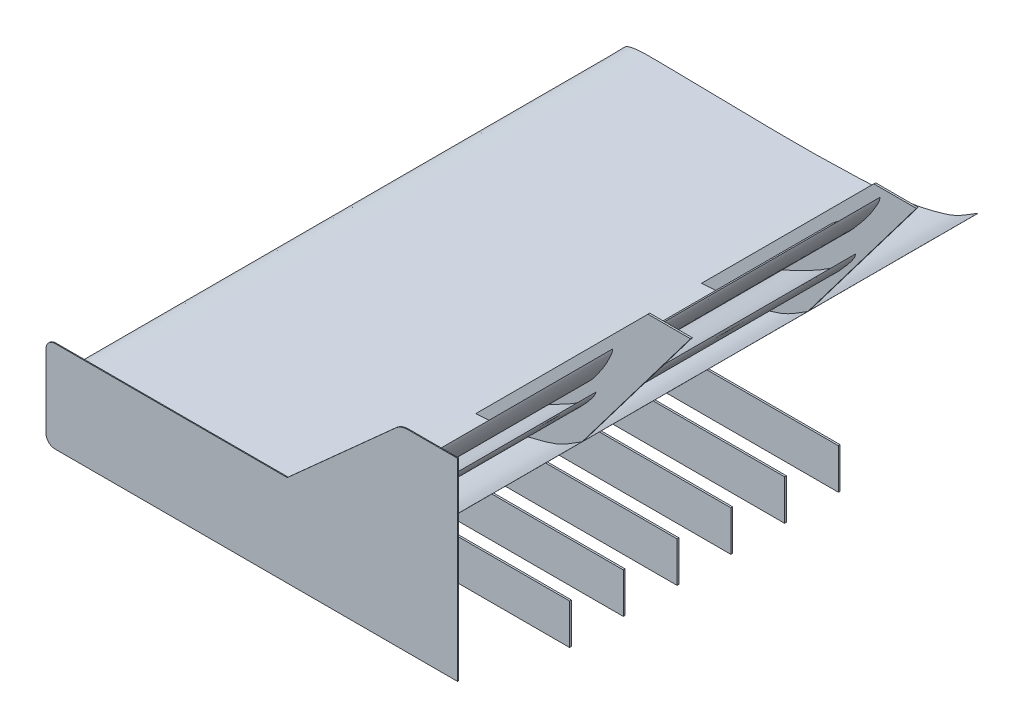
SolidWorks part; units mm, degrees
ref_plane "Front Plane" through (0, 0, 0) normal (0, 0, 1) x (1, 0, 0)
ref_plane "Top Plane" through (0, 0, 0) normal (0, 1, 0) x (1, 0, 0)
ref_plane "Right Plane" through (0, 0, 0) normal (1, 0, 0) x (0, 0, -1)
sketch "Sketch1" plane through (0, 0, 0) normal (0, 0, 1) x (1, 0, 0)
  line L0 (0, 0) -> (100, 0) construction
  line L1 (1.25, 16.6531) -> (1.25, -38.4553) construction
  line L2 (2.5, 17.9055) -> (2.5, -38.4614) construction
  line L3 (0, 16.6233) -> (0, -25.6938) construction
  line L4 (2.5, -38.4553) -> (2.5, 17.9055) construction
  line L6 (5, 17.9055) -> (5, -38.4553) construction
  line L8 (7.5, -38.4553) -> (7.5, 17.9055) construction
  line L10 (10, 17.9055) -> (10, -38.4553) construction
  line L12 (15, -38.4553) -> (15, 17.9055) construction
  line L14 (20, 17.9055) -> (20, -38.4553) construction
  line L16 (30, -38.4553) -> (30, 17.9055) construction
  line L18 (40, 17.9055) -> (40, -38.4553) construction
  line L20 (50, -38.4553) -> (50, 17.9055) construction
  line L22 (60, 17.9055) -> (60, -38.4553) construction
  line L24 (70, -38.4553) -> (70, 17.9055) construction
  line L26 (80, 17.9055) -> (80, -38.4553) construction
  line L28 (90, -38.4553) -> (90, 17.9055) construction
  line L30 (95, 17.9055) -> (95, -38.4553) construction
  line L32 (100, -38.4553) -> (100, 17.9055) construction
  spline S2 degree 3 poles (94.3673, -3.5638) (102.8561, 1.5222) (94.504, -2.988) (88.8138, -4.3065) (79.9056, -5.4947) (70.0198, -5.0741) (59.9849, -4.387) (49.9902, -3.5342) (39.9927, -2.4103) (30.0039, -1.1606) (21.6652, -0.2167) (14.9997, 0.5924) (10.0103, 1.184) (5.8366, 1.6528) (2.898, 1.5692) (0.8648, 1.1108) (-0.6238, -1.2668) (0.9385, -3.7627) (2.7533, -5.9838) (4.8768, -7.8493) (7.4255, -9.5789) (10.7358, -11.3943) (14.9019, -13.1207) (21.5668, -15.0457) (29.9416, -16.4142) (39.9918, -17.0298) (50.051, -16.6825) (60.0771, -15.2123) (70.1301, -12.7919) (80.007, -9.774) (88.8716, -6.1499) (94.3673, -3.5638) (102.8561, 1.5222) (94.504, -2.988) knots -0.105257 -0.054131 -0.027635 0 0.026268 0.051016 0.098804 0.146246 0.193788 0.241403 0.289125 0.336907 0.384666 0.408554 0.432437 0.456234 0.468112 0.474323 0.485191 0.50162 0.510955 0.52691 0.541278 0.554823 0.580548 0.60527 0.653411 0.700937 0.748406 0.796324 0.845052 0.894743 0.945869 0.972365 1 1.026268 1.051016 1.098804 only from (100, -0.1) to (100, -0.1)
  point P37 (0, -0.86)
  point P38 (1.25, -4.09)
  point P40 (1.25, 1.06)
  point P41 (2.5, 1.45)
  point P42 (5, -7.86)
  point P43 (2.5, -5.61)
  point P44 (5, 1.59)
  point P45 (7.5, -9.57)
  point P46 (7.5, 1.44)
  point P47 (10, 1.18)
  point P48 (15, 0.59)
  point P49 (15, -13.05)
  point P50 (20, -0.01)
  point P51 (20, -14.52)
  point P52 (30, -1.18)
  point P53 (30, -16.25)
  point P54 (40, -2.39)
  point P55 (10, -10.95)
  point P56 (40, -16.87)
  point P57 (40, -2.39)
  point P58 (50, -3.49)
  point P59 (50, -16.5)
  point P60 (60, -4.36)
  point P61 (60, -15.07)
  point P62 (70, -5.03)
  point P63 (70, -12.72)
  point P64 (80, -5.19)
  point P65 (80, -9.6)
  point P66 (90, -3.97)
  point P67 (90, -5.58)
  point P68 (95, -2.48)
  point P69 (95, -3.09)
  point P70 (100, -0.1)
  point P71 (100, -0.2)
  dimension "D1" = 100
  dimension "D2" = 1.25
  dimension "D3" = 2.5
  dimension "D4" = 2.5
  dimension "D5" = 7.5
  dimension "D6" = 10
  dimension "D7" = 15
  dimension "D8" = 5
  dimension "D9" = 10
  dimension "D10" = 10
  dimension "D11" = 10
  dimension "D12" = 10
  dimension "D13" = 10
  dimension "D14" = 10
  dimension "D15" = 10
  dimension "D16" = 5
  dimension "D17" = 5
curve "Curve1"
  spline degree 3 poles (98.5502, -0.8292, 0) (100.5299, 0.3794, 0) (99.1462, -0.6768, 0) (98.4443, -1.2755, 0) (97.3097, -2.0642, 0) (96.0009, -2.7117, 0) (94.4298, -3.3947, 0) (92.569, -4.0837, 0) (90.4012, -4.8122, 0) (87.9505, -5.5478, 0) (85.2749, -6.304, 0) (82.4359, -7.0338, 0) (79.5022, -7.7406, 0) (76.5208, -8.4057, 0) (73.5219, -9.0393, 0) (70.5175, -9.6161, 0) (67.5077, -10.1489, 0) (64.4881, -10.6321, 0) (61.4395, -11.0484, 0) (58.3521, -11.4274, 0) (55.2125, -11.781, 0) (52.0112, -12.0861, 0) (48.7533, -12.37, 0) (45.4544, -12.6663, 0) (42.1402, -12.9291, 0) (38.8572, -13.1898, 0) (35.6511, -13.4329, 0) (32.5711, -13.6325, 0) (29.6613, -13.7858, 0) (26.9506, -13.8772, 0) (24.4353, -13.8571, 0) (22.088, -13.7476, 0) (19.8826, -13.5013, 0) (17.7867, -13.168, 0) (15.7934, -12.7056, 0) (13.8906, -12.1349, 0) (12.076, -11.4655, 0) (10.3558, -10.6964, 0) (8.7488, -9.8421, 0) (7.2684, -8.933, 0) (5.9416, -8.0004, 0) (4.7755, -7.0863, 0) (3.7847, -6.217, 0) (2.957, -5.4094, 0) (2.269, -4.6735, 0) (1.728, -3.9816, 0) (1.2751, -3.3596, 0) (0.9309, -2.7719, 0) (0.6318, -2.2442, 0) (0.4105, -1.7465, 0) (0.2408, -1.2843, 0) (0.1068, -0.8552, 0) (0.0223, -0.45, 0) (-0.004, -0.0672, 0) (-0.0039, 0.3013, 0) (0.0809, 0.6622, 0) (0.2952, 0.9824, 0) (0.6315, 1.1995, 0) (1.032, 1.3336, 0) (1.4872, 1.4186, 0) (2.0055, 1.4764, 0) (2.6028, 1.5163, 0) (3.3032, 1.5313, 0) (4.1367, 1.5461, 0) (5.1573, 1.5223, 0) (6.4269, 1.4548, 0) (8.0274, 1.3654, 0) (10.0021, 1.2291, 0) (12.3384, 1.004, 0) (14.971, 0.7256, 0) (17.8195, 0.3367, 0) (20.844, -0.1077, 0) (24.0032, -0.6376, 0) (27.2668, -1.1722, 0) (30.5738, -1.7172, 0) (33.8785, -2.2723, 0) (37.1527, -2.7975, 0) (40.3807, -3.3138, 0) (43.5644, -3.7828, 0) (46.6972, -4.2145, 0) (49.7874, -4.5959, 0) (52.8339, -4.9281, 0) (55.8477, -5.1987, 0) (58.8316, -5.4085, 0) (61.7919, -5.5626, 0) (64.7329, -5.6385, 0) (67.6568, -5.6622, 0) (70.5644, -5.6128, 0) (73.4581, -5.4881, 0) (76.3366, -5.3163, 0) (79.1931, -5.05, 0) (82.0171, -4.7312, 0) (84.7804, -4.3625, 0) (87.434, -3.9036, 0) (89.9332, -3.4404, 0) (92.2075, -2.9247, 0) (94.233, -2.3848, 0) (95.9446, -1.8589, 0) (97.5056, -1.2357, 0) (98.5502, -0.8292, 0) (100.5299, 0.3794, 0) (99.1462, -0.6768, 0) knots -0.020778 -0.013318 -0.006872 0 0.003934 0.00967 0.015849 0.022782 0.030794 0.040273 0.051195 0.063508 0.076888 0.09098 0.105453 0.12007 0.134692 0.149314 0.163846 0.178433 0.193072 0.207875 0.222946 0.238282 0.253894 0.269743 0.28568 0.30147 0.316872 0.331691 0.345638 0.35857 0.370496 0.381625 0.392182 0.402235 0.411978 0.42144 0.430647 0.439636 0.448385 0.456672 0.46448 0.47158 0.477867 0.483331 0.488125 0.492267 0.495894 0.499125 0.502007 0.504569 0.506909 0.509051 0.510997 0.512815 0.514533 0.516257 0.518043 0.519896 0.521872 0.524061 0.526511 0.529332 0.532624 0.536536 0.54126 0.547229 0.554731 0.564199 0.575553 0.588316 0.602079 0.616691 0.632061 0.647918 0.664017 0.680023 0.695872 0.71147 0.726804 0.741922 0.756725 0.771359 0.785775 0.800025 0.814163 0.828192 0.842121 0.856004 0.869802 0.883566 0.897265 0.910851 0.924235 0.937151 0.949387 0.960589 0.970563 0.979222 0.986682 0.993128 1 1.003934 1.00967 1.015849 periodic
sketch "Sketch2" plane through (0, 0, 0) normal (0, 0, 1) x (1, 0, 0)
  line L0 (331.6325, -0.1558) -> (-65.7962, -45.4371) construction
  line L1 (-65.7962, -45.4371) -> (-68.337, -23.1365) construction
  line L2 (0, 0) -> (60.5483, 0) construction
  line L3 (385.2571, 82.501) -> (286.9589, 13.6718) construction
  line L4 (286.9589, 13.6718) -> (272.478, 34.3526) construction
  line L5 (331.6325, -0.1558) -> (331.6325, 76.9311) construction
  line L6 (331.6325, -0.1558) -> (397.2706, -0.1558) construction
  line L7 (412.1546, 150.4845) -> (355.5861, 93.9159) construction
  line L8 (299.294, 9.8442) -> (308.8152, 9.8442) construction
  line L9 (286.6325, 14.5606) -> (286.6325, 26.1748) construction
  line L10 (355.5861, 93.9159) -> (325.5679, 123.9341) construction
  line L11 (385.2571, 82.501) -> (439.2948, 82.501) construction
  line L12 (385.2571, 82.501) -> (385.2571, 253.7541) construction
  line L14 (360.5365, 92.501) -> (347.2815, 92.501) construction
  line L15 (355.2571, 94.5953) -> (355.2571, 86.9128) construction
  spline S1 degree 3 poles (384.8846, 81.2478) (385.5164, 83.2388) (384.4039, 80.6874) (383.6577, 79.5684) (382.5534, 77.8807) (381.234, 76.1849) (379.6159, 74.2589) (377.7366, 72.1854) (375.6004, 70.0085) (373.3094, 67.7296) (370.8484, 65.4636) (368.2936, 63.2048) (365.6704, 60.9752) (362.9606, 58.8233) (360.2036, 56.7073) (357.3809, 54.6556) (354.4918, 52.6644) (351.55, 50.7129) (348.5353, 48.8248) (345.4591, 46.9752) (342.3116, 45.1647) (339.0895, 43.3924) (335.7907, 41.6382) (332.4153, 39.904) (328.9642, 38.1714) (325.437, 36.4548) (321.8583, 34.7152) (318.229, 32.9837) (314.6045, 31.2409) (311.0296, 29.5177) (307.5607, 27.8619) (304.283, 26.2148) (301.2163, 24.6344) (298.438, 23.0944) (295.9876, 21.7059) (293.9535, 20.4794) (292.3194, 19.4647) (291.0255, 18.6563) (290.0064, 17.9765) (289.1977, 17.3878) (288.5198, 16.8905) (287.9605, 16.4397) (287.4911, 16.026) (287.1025, 15.6288) (286.8013, 15.2211) (286.6204, 14.7762) (286.6306, 14.3139) (286.7959, 13.9009) (287.0496, 13.5387) (287.3391, 13.1808) (287.7014, 12.8408) (288.1286, 12.5116) (288.6138, 12.1745) (289.1741, 11.8379) (289.8315, 11.5255) (290.5746, 11.1852) (291.4481, 10.8861) (292.4563, 10.579) (293.6392, 10.33) (295.0088, 10.1068) (296.5811, 9.9353) (298.3566, 9.8405) (300.3027, 9.8384) (302.3835, 9.9651) (304.5509, 10.2329) (306.7709, 10.6623) (309.0149, 11.2548) (311.2776, 12.005) (313.5546, 12.9239) (315.8434, 14.0403) (318.1798, 15.3178) (320.5616, 16.8273) (323.0467, 18.5404) (325.647, 20.4977) (328.4002, 22.653) (331.2889, 24.971) (334.2713, 27.4186) (337.3173, 29.9365) (340.3924, 32.4781) (343.4295, 35.0419) (346.4347, 37.5652) (349.3698, 40.0706) (352.2108, 42.5809) (354.9831, 45.0803) (357.6916, 47.5896) (360.3254, 50.1446) (362.9155, 52.7417) (365.4699, 55.3783) (367.9798, 58.0668) (370.4509, 60.7742) (372.8463, 63.4898) (375.1328, 66.1627) (377.2406, 68.7489) (379.1415, 71.1601) (380.7696, 73.3693) (382.1232, 75.3282) (383.1961, 77.0817) (384.0359, 78.6195) (384.6074, 80.1761) (384.8846, 81.2478) (385.5164, 83.2388) (384.4039, 80.6874) knots -0.015849 -0.00967 -0.003934 0 0.006872 0.013318 0.020778 0.029437 0.039411 0.050613 0.062849 0.075765 0.089149 0.102735 0.116434 0.130198 0.143996 0.157879 0.171808 0.185837 0.199975 0.214225 0.228641 0.243275 0.258078 0.273196 0.28853 0.304128 0.319977 0.335983 0.352082 0.367939 0.383309 0.397921 0.411684 0.424447 0.435801 0.445269 0.452771 0.45874 0.463464 0.467376 0.470668 0.473489 0.475939 0.478128 0.480104 0.481957 0.483743 0.485467 0.487185 0.489003 0.490949 0.493091 0.495431 0.497993 0.500875 0.504106 0.507733 0.511875 0.516669 0.522133 0.52842 0.53552 0.543328 0.551615 0.560364 0.569353 0.57856 0.588022 0.597765 0.607818 0.618375 0.629504 0.64143 0.654362 0.668309 0.683128 0.69853 0.71432 0.730257 0.746106 0.761718 0.777054 0.792125 0.806928 0.821567 0.836154 0.850686 0.865308 0.87993 0.894547 0.90902 0.923112 0.936492 0.948805 0.959727 0.969206 0.977218 0.984151 0.99033 0.996066 1 1.006872 1.013318 1.020778 only from (385.2571, 82.501) to (385.2571, 82.501)
  spline S2 degree 3 poles (310.6391, -16.2329) (342.3319, 7.4626) (310.948, -13.8864) (288.8507, -21.4531) (253.8988, -29.8144) (214.402, -32.1744) (174.2032, -33.5355) (134.0967, -34.2209) (93.8685, -33.8291) (53.6236, -32.9335) (20.0676, -32.5806) (-6.7778, -32.082) (-26.867, -31.764) (-43.661, -31.6021) (-55.3165, -33.1337) (-63.2173, -35.7866) (-68.169, -45.8522) (-60.9356, -55.1433) (-52.8102, -63.238) (-43.602, -69.7925) (-32.7577, -75.633) (-18.8487, -81.5041) (-1.572, -86.6718) (25.7261, -91.6102) (59.5991, -93.6371) (99.8297, -91.9854) (139.7029, -86.4995) (178.9865, -76.5608) (217.9897, -62.8307) (256.0482, -46.7957) (289.8325, -28.7623) (310.6391, -16.2329) (342.3319, 7.4626) (310.948, -13.8864) knots -0.105257 -0.054131 -0.027635 0 0.026268 0.051016 0.098804 0.146246 0.193788 0.241403 0.289125 0.336907 0.384666 0.408554 0.432437 0.456234 0.468112 0.474323 0.485191 0.50162 0.510955 0.52691 0.541278 0.554823 0.580548 0.60527 0.653411 0.700937 0.748406 0.796324 0.845052 0.894743 0.945869 0.972365 1 1.026268 1.051016 1.098804 only from (331.6325, -0.1558) to (331.6325, -0.1558)
  spline S3 degree 3 poles (412.0551, 149.6186) (412.2394, 150.9988) (411.8044, 149.195) (411.444, 148.3739) (410.9144, 147.1381) (410.2444, 145.8719) (409.4051, 144.4202) (408.4113, 142.8413) (407.2608, 141.1648) (406.0205, 139.4033) (404.6671, 137.6307) (403.2512, 135.852) (401.7872, 134.0845) (400.2572, 132.358) (398.692, 130.6496) (397.0763, 128.9757) (395.41, 127.334) (393.7045, 125.7123) (391.9439, 124.1236) (390.1384, 122.5532) (388.2815, 121.0002) (386.3712, 119.4635) (384.4085, 117.9299) (382.3932, 116.4006) (380.328, 114.8636) (378.211, 113.3282) (376.0628, 111.7718) (373.8805, 110.2149) (371.7026, 108.6511) (369.5551, 107.1059) (367.4692, 105.6172) (365.508, 104.1564) (363.6776, 102.7638) (362.0318, 101.4311) (360.5837, 100.2358) (359.3903, 99.1951) (358.4349, 98.3397) (357.6789, 97.6592) (357.0886, 97.0949) (356.6258, 96.6148) (356.2383, 96.2098) (355.9233, 95.8491) (355.663, 95.5231) (355.4538, 95.2174) (355.3033, 94.9148) (355.236, 94.6018) (355.2962, 94.2995) (355.4525, 94.0475) (355.6611, 93.839) (355.8926, 93.6376) (356.1697, 93.4563) (356.4883, 93.2896) (356.846, 93.1244) (357.2528, 92.9683) (357.7205, 92.8393) (358.2478, 92.7019) (358.8559, 92.6067) (359.5534, 92.5218) (360.3589, 92.4952) (361.2839, 92.5073) (362.336, 92.5766) (363.5127, 92.72) (364.7906, 92.9439) (366.142, 93.2679) (367.534, 93.6947) (368.9418, 94.2336) (370.3465, 94.8823) (371.7452, 95.6368) (373.1338, 96.5037) (374.5072, 97.5017) (375.8933, 98.6108) (377.2822, 99.8777) (378.7155, 101.29) (380.1961, 102.8761) (381.7542, 104.6099) (383.3824, 106.4662) (385.0571, 108.4184) (386.7654, 110.4241) (388.4901, 112.4487) (390.1873, 114.4835) (391.8682, 116.4881) (393.5052, 118.4728) (395.0798, 120.4498) (396.6106, 122.4116) (398.0983, 124.3726) (399.5317, 126.355) (400.9316, 128.3599) (402.3034, 130.3867) (403.6401, 132.4423) (404.949, 134.5059) (406.2072, 136.5661) (407.399, 138.5857) (408.4835, 140.5277) (409.4524, 142.3307) (410.2655, 143.9697) (410.9274, 145.4124) (411.4289, 146.6879) (411.8022, 147.7947) (411.9972, 148.8829) (412.0551, 149.6186) (412.2394, 150.9988) (411.8044, 149.195) knots -0.015849 -0.00967 -0.003934 0 0.006872 0.013318 0.020778 0.029437 0.039411 0.050613 0.062849 0.075765 0.089149 0.102735 0.116434 0.130198 0.143996 0.157879 0.171808 0.185837 0.199975 0.214225 0.228641 0.243275 0.258078 0.273196 0.28853 0.304128 0.319977 0.335983 0.352082 0.367939 0.383309 0.397921 0.411684 0.424447 0.435801 0.445269 0.452771 0.45874 0.463464 0.467376 0.470668 0.473489 0.475939 0.478128 0.480104 0.481957 0.483743 0.485467 0.487185 0.489003 0.490949 0.493091 0.495431 0.497993 0.500875 0.504106 0.507733 0.511875 0.516669 0.522133 0.52842 0.53552 0.543328 0.551615 0.560364 0.569353 0.57856 0.588022 0.597765 0.607818 0.618375 0.629504 0.64143 0.654362 0.668309 0.683128 0.69853 0.71432 0.730257 0.746106 0.761718 0.777054 0.792125 0.806928 0.821567 0.836154 0.850686 0.865308 0.87993 0.894547 0.90902 0.923112 0.936492 0.948805 0.959727 0.969206 0.977218 0.984151 0.99033 0.996066 1 1.006872 1.013318 1.020778 only from (412.1546, 150.4845) to (412.1546, 150.4845)
  dimension "D2" = 400
  dimension "D1" = 90
  dimension "D3" = 6.5
  dimension "D4" = 90
  dimension "D5" = 120
  dimension "D6" = 35
  dimension "D7" = 10
  dimension "D8" = 45
  dimension "D9" = 90
  dimension "D10" = 80
  dimension "D11" = 45
  dimension "D12" = 30
  dimension "D13" = 10
extrude "Boss-Extrude1" add sketch "Sketch2" along normal blind 450 and the other way blind 190 contours S2
extrude "Boss-Extrude2" add sketch "Sketch2<3>" along normal blind 250 separate body contours S1
sketch "Sketch2<3>" plane through (0, 0, 0) normal (0, 0, 1) x (1, 0, 0) same geometry as "Sketch2"
extrude "Boss-Extrude3" add sketch "Sketch2<4>" along normal blind 250 separate body contours S3
sketch "Sketch2<4>" plane through (0, 0, 0) normal (0, 0, 1) x (1, 0, 0) same geometry as "Sketch2"
sketch "Sketch3" plane through (0, 0, 0) normal (0, 0, 1) x (1, 0, 0)
  line L0 (213.126, -32.0618) -> (405.3691, 160.1813)
  line L1 (405.3691, 160.1813) -> (452.8645, 160.1813)
  line L2 (452.8645, 160.1813) -> (331.6325, -0.1558)
  spline S0 degree 3 poles (310.6391, -16.2329) (342.3319, 7.4626) (310.948, -13.8864) (288.8507, -21.4531) (253.8988, -29.8144) (214.402, -32.1744) (174.2032, -33.5355) (134.0967, -34.2209) (93.8685, -33.8291) (53.6236, -32.9335) (20.0676, -32.5806) (-6.7778, -32.082) (-26.867, -31.764) (-43.661, -31.6021) (-55.3165, -33.1337) (-63.2173, -35.7866) (-68.169, -45.8522) (-60.9356, -55.1433) (-52.8102, -63.238) (-43.602, -69.7925) (-32.7577, -75.633) (-18.8487, -81.5041) (-1.572, -86.6718) (25.7261, -91.6102) (59.5991, -93.6371) (99.8297, -91.9854) (139.7029, -86.4995) (178.9865, -76.5608) (217.9897, -62.8307) (256.0482, -46.7957) (289.8325, -28.7623) (310.6391, -16.2329) (342.3319, 7.4626) (310.948, -13.8864) knots -0.105257 -0.054131 -0.027635 0 0.026268 0.051016 0.098804 0.146246 0.193788 0.241403 0.289125 0.336907 0.384666 0.408554 0.432437 0.456234 0.468112 0.474323 0.485191 0.50162 0.510955 0.52691 0.541278 0.554823 0.580548 0.60527 0.653411 0.700937 0.748406 0.796324 0.845052 0.894743 0.945869 0.972365 1 1.026268 1.051016 1.098804 only from (331.6325, -0.1558) to (331.6325, -0.1558) construction
  spline S1 degree 3 poles (331.6325, -0.1558) (331.3048, -0.0386) (310.948, -13.8864) (288.8507, -21.4531) (253.8988, -29.8144) (227.165, -31.4118) (213.5191, -32.0438) (213.126, -32.0618) knots 0 0 0 0 0.026268 0.051016 0.098804 0.146246 0.147653 0.147653 0.147653 0.147653
extrude "Boss-Extrude4" add sketch "Sketch3" against normal blind 2
ref_plane "Plane1" through (0, 0, 125) normal (0, 0, 1) x (1, 0, 0)
ref_plane "Plane5" through (0, 0, 260) normal (0, 0, 1) x (1, 0, 0)
sketch "Sketch5" plane through (0, 0, 260) normal (0, 0, 1) x (1, 0, 0)
  line L0 (58.7057, 9.8442) -> (504.5594, 9.8442) construction
  line L1 (347.1647, 55.7303) -> (281.6325, 9.8442) construction
  line L2 (365.732, 106.693) -> (327.1647, 60.7303) construction
  line L3 (202.2247, 55.7303) -> (492.1047, 55.7303) construction
  line L5 (492.1047, 60.7303) -> (202.2247, 60.7303) construction
  spline S2 degree 3 poles (365.7201, 106.0373) (365.7582, 107.0844) (365.5631, 105.7019) (365.3526, 105.0609) (365.0454, 104.097) (364.6353, 103.1002) (364.1118, 101.9522) (363.4818, 100.6978) (362.7415, 99.3589) (361.9401, 97.9499) (361.0549, 96.5244) (360.1233, 95.0897) (359.1548, 93.66) (358.1339, 92.2562) (357.0854, 90.8634) (355.9965, 89.4929) (354.8674, 88.1427) (353.7076, 86.8046) (352.504, 85.4874) (351.2654, 84.1805) (349.9872, 82.883) (348.6678, 81.5939) (347.3089, 80.3032) (345.9103, 79.012) (344.4749, 77.7114) (343.0005, 76.4082) (341.5044, 75.087) (339.9827, 73.763) (338.4648, 72.4342) (336.9683, 71.1215) (335.5139, 69.8555) (334.1508, 68.6195) (332.8808, 67.444) (331.7447, 66.3268) (330.7468, 65.3268) (329.9283, 64.4609) (329.2747, 63.7511) (328.7578, 63.1867) (328.3565, 62.7214) (328.0447, 62.3283) (327.7838, 61.997) (327.574, 61.704) (327.4027, 61.441) (327.2681, 61.1969) (327.1773, 60.9594) (327.1496, 60.7201) (327.2165, 60.498) (327.3519, 60.3206) (327.5231, 60.1796) (327.7111, 60.0455) (327.9318, 59.9298) (328.1825, 59.8281) (328.4623, 59.7302) (328.7782, 59.6428) (329.1379, 59.58) (329.5427, 59.5153) (330.0051, 59.488) (330.5336, 59.4749) (331.1387, 59.5133) (331.8306, 59.5893) (332.6136, 59.7174) (333.4845, 59.91) (334.4253, 60.1702) (335.414, 60.5107) (336.4256, 60.9311) (337.4409, 61.4366) (338.446, 62.0242) (339.4389, 62.6905) (340.4161, 63.4403) (341.3724, 64.2871) (342.3302, 65.2181) (343.2787, 66.2674) (344.2499, 67.429) (345.2439, 68.724) (346.2853, 70.1353) (347.3703, 71.6434) (348.4832, 73.2267) (349.6174, 74.8525) (350.7625, 76.4937) (351.8863, 78.1405) (353.0001, 79.7634) (354.0824, 81.3683) (355.1185, 82.963) (356.1229, 84.5431) (357.0952, 86.1194) (358.0252, 87.7079) (358.9284, 89.3108) (359.8091, 90.928) (360.6613, 92.5643) (361.4922, 94.2045) (362.2854, 95.8386) (363.0318, 97.4374) (363.7034, 98.9703) (364.2985, 100.3908) (364.7888, 101.6771) (365.1801, 102.8056) (365.4633, 103.7971) (365.6628, 104.653) (365.73, 105.4821) (365.7201, 106.0373) (365.7582, 107.0844) (365.5631, 105.7019) knots -0.015849 -0.00967 -0.003934 0 0.006872 0.013318 0.020778 0.029437 0.039411 0.050613 0.062849 0.075765 0.089149 0.102735 0.116434 0.130198 0.143996 0.157879 0.171808 0.185837 0.199975 0.214225 0.228641 0.243275 0.258078 0.273196 0.28853 0.304128 0.319977 0.335983 0.352082 0.367939 0.383309 0.397921 0.411684 0.424447 0.435801 0.445269 0.452771 0.45874 0.463464 0.467376 0.470668 0.473489 0.475939 0.478128 0.480104 0.481957 0.483743 0.485467 0.487185 0.489003 0.490949 0.493091 0.495431 0.497993 0.500875 0.504106 0.507733 0.511875 0.516669 0.522133 0.52842 0.53552 0.543328 0.551615 0.560364 0.569353 0.57856 0.588022 0.597765 0.607818 0.618375 0.629504 0.64143 0.654362 0.668309 0.683128 0.69853 0.71432 0.730257 0.746106 0.761718 0.777054 0.792125 0.806928 0.821567 0.836154 0.850686 0.865308 0.87993 0.894547 0.90902 0.923112 0.936492 0.948805 0.959727 0.969206 0.977218 0.984151 0.99033 0.996066 1 1.006872 1.013318 1.020778 only from (365.732, 106.693) to (365.732, 106.693)
  spline S3 degree 3 poles (346.9241, 54.878) (347.3334, 56.2324) (346.6038, 54.494) (346.1089, 53.7291) (345.3767, 52.5757) (344.499, 51.4147) (343.4211, 50.0951) (342.1677, 48.6732) (340.7412, 47.1787) (339.2108, 45.6137) (337.5652, 44.0559) (335.856, 42.5021) (334.1002, 40.9674) (332.285, 39.4846) (330.4375, 38.0256) (328.5449, 36.6095) (326.6068, 35.2338) (324.6326, 33.8846) (322.6084, 32.5775) (320.5422, 31.296) (318.4274, 30.0402) (316.2616, 28.8096) (314.0438, 27.5906) (311.7738, 26.3844) (309.4526, 25.1787) (307.0797, 23.983) (304.6722, 22.7712) (302.2303, 21.5645) (299.7917, 20.3502) (297.3866, 19.1496) (295.0526, 17.9955) (292.848, 16.8493) (290.7858, 15.7502) (288.9184, 14.6811) (287.2718, 13.7177) (285.9056, 12.8679) (284.8083, 12.1654) (283.9395, 11.6057) (283.2556, 11.1358) (282.7134, 10.7295) (282.2589, 10.3863) (281.8843, 10.0758) (281.5703, 9.7911) (281.3108, 9.5185) (281.1106, 9.2395) (280.9923, 8.9365) (281.0035, 8.6235) (281.1193, 8.3453) (281.2945, 8.1024) (281.494, 7.8627) (281.7425, 7.6358) (282.0349, 7.4168) (282.3668, 7.193) (282.7494, 6.9703) (283.1976, 6.7648) (283.704, 6.5413) (284.2985, 6.347) (284.9842, 6.1484) (285.7877, 5.9908) (286.7174, 5.8525) (287.784, 5.751) (288.9874, 5.7035) (290.3055, 5.7203) (291.7136, 5.8255) (293.1791, 6.0272) (294.6787, 6.3389) (296.193, 6.7612) (297.7185, 7.2905) (299.2522, 7.9342) (300.7919, 8.7118) (302.3624, 9.5989) (303.9614, 10.6436) (305.6286, 11.8271) (307.3714, 13.1772) (309.216, 14.6628) (311.1507, 16.2598) (313.1478, 17.9455) (315.1873, 19.6794) (317.2463, 21.4296) (319.2793, 23.1945) (321.2911, 24.9317) (323.2556, 26.6561) (325.1562, 28.3829) (327.0105, 30.1017) (328.8215, 31.8266) (330.5814, 33.5818) (332.3114, 35.3651) (334.0168, 37.1748) (335.6916, 39.0192) (337.3399, 40.8761) (338.9369, 42.7378) (340.4605, 44.5696) (341.8639, 46.341) (343.1288, 47.9918) (344.2108, 49.5034) (345.1093, 50.8428) (345.8195, 52.0405) (346.374, 53.0899) (346.7464, 54.1496) (346.9241, 54.878) (347.3334, 56.2324) (346.6038, 54.494) knots -0.015849 -0.00967 -0.003934 0 0.006872 0.013318 0.020778 0.029437 0.039411 0.050613 0.062849 0.075765 0.089149 0.102735 0.116434 0.130198 0.143996 0.157879 0.171808 0.185837 0.199975 0.214225 0.228641 0.243275 0.258078 0.273196 0.28853 0.304128 0.319977 0.335983 0.352082 0.367939 0.383309 0.397921 0.411684 0.424447 0.435801 0.445269 0.452771 0.45874 0.463464 0.467376 0.470668 0.473489 0.475939 0.478128 0.480104 0.481957 0.483743 0.485467 0.487185 0.489003 0.490949 0.493091 0.495431 0.497993 0.500875 0.504106 0.507733 0.511875 0.516669 0.522133 0.52842 0.53552 0.543328 0.551615 0.560364 0.569353 0.57856 0.588022 0.597765 0.607818 0.618375 0.629504 0.64143 0.654362 0.668309 0.683128 0.69853 0.71432 0.730257 0.746106 0.761718 0.777054 0.792125 0.806928 0.821567 0.836154 0.850686 0.865308 0.87993 0.894547 0.90902 0.923112 0.936492 0.948805 0.959727 0.969206 0.977218 0.984151 0.99033 0.996066 1 1.006872 1.013318 1.020778 only from (347.1647, 55.7303) to (347.1647, 55.7303)
  point P5 (281.6325, 9.8442)
  point P10 (318.2893, 61.9198)
  point P13 (347.1647, 55.7303)
  point P16 (323.8582, 65.7303)
  point P17 (332.1647, 60.7303)
  dimension "D1" = 80
  dimension "D2" = 50
  dimension "D3" = 10
  dimension "D4" = 60
  dimension "D5" = 5
  dimension "D6" = 35
  dimension "D7" = 50
  dimension "D8" = 20
mirror "Mirror1" about plane through (0, 0, 125) normal (0, 0, 1) of "Boss-Extrude4"
ref_plane "Plane2" through (0, 0, 185) normal (0, 0, 1) x (1, 0, 0)
ref_plane "Plane3" through (0, 0, 65) normal (0, 0, 1) x (1, 0, 0)
sketch "Sketch4" plane through (0, 0, 65) normal (0, 0, 1) x (1, 0, 0)
  line L0 (78.3177, -92.7012) -> (430.8358, -92.7012)
  line L1 (430.8358, -92.7012) -> (430.8358, -47.7012)
  line L2 (430.8358, -47.7012) -> (252.5788, -47.7012)
  spline S0 degree 3 poles (310.6391, -16.2329) (342.3319, 7.4626) (310.948, -13.8864) (288.8507, -21.4531) (253.8988, -29.8144) (214.402, -32.1744) (174.2032, -33.5355) (134.0967, -34.2209) (93.8685, -33.8291) (53.6236, -32.9335) (20.0676, -32.5806) (-6.7778, -32.082) (-26.867, -31.764) (-43.661, -31.6021) (-55.3165, -33.1337) (-63.2173, -35.7866) (-68.169, -45.8522) (-60.9356, -55.1433) (-52.8102, -63.238) (-43.602, -69.7925) (-32.7577, -75.633) (-18.8487, -81.5041) (-1.572, -86.6718) (25.7261, -91.6102) (59.5991, -93.6371) (99.8297, -91.9854) (139.7029, -86.4995) (178.9865, -76.5608) (217.9897, -62.8307) (256.0482, -46.7957) (289.8325, -28.7623) (310.6391, -16.2329) (342.3319, 7.4626) (310.948, -13.8864) knots -0.105257 -0.054131 -0.027635 0 0.026268 0.051016 0.098804 0.146246 0.193788 0.241403 0.289125 0.336907 0.384666 0.408554 0.432437 0.456234 0.468112 0.474323 0.485191 0.50162 0.510955 0.52691 0.541278 0.554823 0.580548 0.60527 0.653411 0.700937 0.748406 0.796324 0.845052 0.894743 0.945869 0.972365 1 1.026268 1.051016 1.098804 only from (331.6325, -0.1558) to (331.6325, -0.1558) construction
  spline S1 degree 3 poles (78.3177, -92.7012) (85.4873, -92.437) (105.9683, -91.1408) (139.7029, -86.4995) (178.9865, -76.5608) (216.8353, -63.237) (240.8302, -53.2039) (252.5788, -47.7012) knots 0.675413 0.675413 0.675413 0.675413 0.700937 0.748406 0.796324 0.845052 0.890412 0.890412 0.890412 0.890412
  dimension "D1" = 45
  dimension "D2" = 45
extrude "Boss-Extrude5" add sketch "Sketch4" against normal blind 2
pattern_linear "LPattern1" count 6 spacing 60 along (0, 0, 1) of "Boss-Extrude5"
ref_plane "Plane4" through (0, 0, -190) normal (0, 0, 1) x (1, 0, 0)
extrude "Boss-Extrude6" add sketch "Sketch5" along normal blind 190 and the other way blind 9 contours S3
extrude "Boss-Extrude7" add sketch "Sketch5<3>" along normal blind 190 and the other way blind 8 contours S2
sketch "Sketch5<3>" plane through (0, 0, 260) normal (0, 0, 1) x (1, 0, 0) same geometry as "Sketch5"
sketch "Sketch7" plane through (0, 0, 450) normal (0, 0, 1) x (1, 0, 0)
  line L0 (0, 0) -> (-57.3889, 0)
  line L1 (-67.3889, -10) -> (-67.3889, -92)
  line L2 (-57.3889, -102) -> (391.8601, -102)
  line L4 (391.8601, -102) -> (391.8601, 113.6145)
  line L5 (391.8601, 113.6145) -> (336.1958, 113.6145)
  line L6 (322.8424, 108.5037) -> (201.86, 0)
  line L7 (201.86, 0) -> (0, 0)
  arc A0 (-67.3889, -92) -> (-57.3889, -102) centre (-57.3889, -92) ccw
  arc A1 (-57.3889, 0) -> (-67.3889, -10) centre (-57.3889, -10) ccw
  arc A2 (336.1958, 113.6145) -> (322.8424, 108.5037) centre (336.1958, 93.6145) ccw
  dimension "D1" = 10
  dimension "D2" = 20
  dimension "D3" = 102
extrude "Boss-Extrude8" add sketch "Sketch7" along normal blind 1
sketch "Sketch9" plane through (0, 0, -190) normal (0, 0, -1) x (-1, 0, 0)
  line L0 (54.3813, -61.4902) -> (-430.8358, -61.4902) construction
  line L1 (-430.8358, -92.7012) -> (-430.8358, -47.7012) construction
  line L2 (54.3813, -61.4902) -> (54.3813, -102) construction
  line L3 (57.3889, -102) -> (-391.8601, -102) construction
  spline S0 degree 3 poles (-310.948, -13.8864) (-342.3319, 7.4626) (-310.6391, -16.2329) (-289.8325, -28.7623) (-256.0482, -46.7957) (-217.9897, -62.8307) (-178.9865, -76.5608) (-139.7029, -86.4995) (-99.8297, -91.9854) (-59.5991, -93.6371) (-25.7261, -91.6102) (1.572, -86.6718) (18.8487, -81.5041) (32.7577, -75.633) (43.602, -69.7925) (52.8102, -63.238) (60.9356, -55.1433) (68.169, -45.8522) (63.2173, -35.7866) (55.3165, -33.1337) (43.661, -31.6021) (26.867, -31.764) (6.7778, -32.082) (-20.0676, -32.5806) (-53.6236, -32.9335) (-93.8685, -33.8291) (-134.0967, -34.2209) (-174.2032, -33.5355) (-214.402, -32.1744) (-253.8988, -29.8144) (-288.8507, -21.4531) (-310.948, -13.8864) (-342.3319, 7.4626) (-310.6391, -16.2329) knots -0.098804 -0.051016 -0.026268 0 0.027635 0.054131 0.105257 0.154948 0.203676 0.251594 0.299063 0.346589 0.39473 0.419452 0.445177 0.458722 0.47309 0.489045 0.49838 0.514809 0.525677 0.531888 0.543766 0.567563 0.591446 0.615334 0.663093 0.710875 0.758597 0.806212 0.853754 0.901196 0.948984 0.973732 1 1.027635 1.054131 1.105257 only from (-331.6325, -0.1558) to (-331.6325, -0.1558) construction
